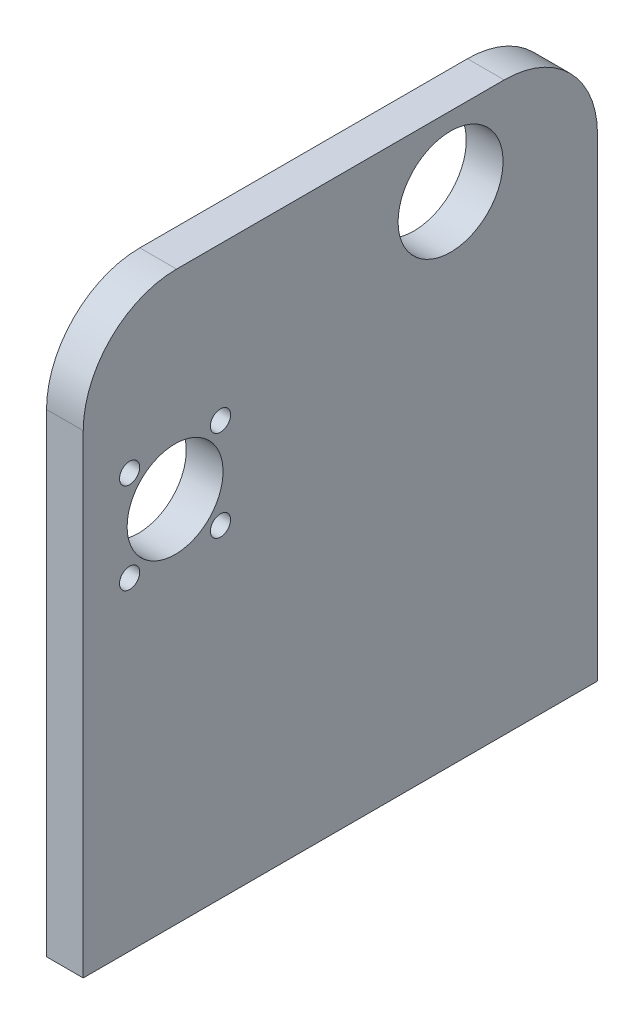
SolidWorks part; units mm, degrees
ref_plane "Front Plane" through (0, 0, 0) normal (0, 0, 1) x (1, 0, 0)
ref_plane "Top Plane" through (0, 0, 0) normal (0, 1, 0) x (1, 0, 0)
ref_plane "Right Plane" through (0, 0, 0) normal (1, 0, 0) x (0, 0, -1)
sketch "Sketch1" plane through (0, 0, 0) normal (0, 1, 0) x (1, 0, 0)
  line L1 (-5, 70) -> (5, 70)
  line L2 (-5, 70) -> (-5, -70)
  line L3 (-5, -70) -> (5, -70)
  line L4 (5, 70) -> (5, -70)
  line L5 (-5, 70) -> (5, -70) construction
  line L6 (-5, -70) -> (5, 70) construction
  point P0 (0, 0)
  dimension "D1" = 140
  dimension "D2" = 10
extrude "Boss-Extrude1" add sketch "Sketch1" along normal mid plane 154.4436
fillet "Fillet1" radius 25.4 2 edges at (0, 77.2218, 70) (0, 77.2218, -70)
sketch "Sketch5" plane through (-5, 0, 0) normal (-1, 0, 0) x (0, 0, 1)
  line L1 (-70, 51.8218) -> (-70, -77.2218) construction
  line L2 (-70, -0.9964) -> (-44.6, -0.9964)
  line L3 (-70, -0.9964) -> (-70, -26.3964)
  line L4 (-70, -26.3964) -> (-44.6, -26.3964)
  line L5 (-70, -77.2218) -> (70, -77.2218) construction
  line L6 (-44.6, -0.9964) -> (-44.6, -26.3964)
  dimension "D3" = 25.4
  dimension "D1" = 50.8254
  dimension "D2" = 25.4
sketch "Sketch3" plane through (-5, 0, 0) normal (-1, 0, 0) x (0, 0, 1)
  line L0 (-45.4613, 35.5412) -> (44.137, 35.5412) construction
  line L1 (-45.4613, 10.797) -> (44.137, 10.797) construction
  line L2 (-70, 51.8218) -> (-70, -77.2218) construction
  line L3 (-45.4613, 23.1718) -> (44.137, 23.1718) construction
  line L4 (32.6342, 46.9613) -> (32.6342, -2.4047) construction
  line L5 (57.3748, 46.9613) -> (57.3748, -2.4047) construction
  line L6 (45, 46.9613) -> (45, -2.4047) construction
  line L7 (-44.6, 77.2218) -> (44.6, 77.2218) construction
  line L8 (70, 51.8218) -> (70, -77.2218) construction
  circle A0 centre (-30, 58.1718) radius 14.29
  circle A1 centre (32.6342, 35.5412) radius 2.75
  circle A2 centre (57.3748, 35.5412) radius 2.75
  circle A3 centre (32.6342, 10.797) radius 2.75
  circle A4 centre (57.3748, 10.797) radius 2.75
  circle A5 centre (45, 23.1718) radius 13.0556
  dimension "D1" = 28.58
  dimension "D2" = 19.05
  dimension "D3" = 12.3658
  dimension "D4" = 12.3748
  dimension "D7" = 26.1112
  dimension "D8" = 5.5
  dimension "D10" = 35
  dimension "D11" = 25
  dimension "D5" = 12.3693
  dimension "D6" = 12.3748
  dimension "D9" = 40
extrude "Cut-Extrude2" cut sketch "Sketch3" against normal blind 28.575
extrude "Cut-Extrude4" [suppressed] cut sketch "Sketch5" against normal through all
